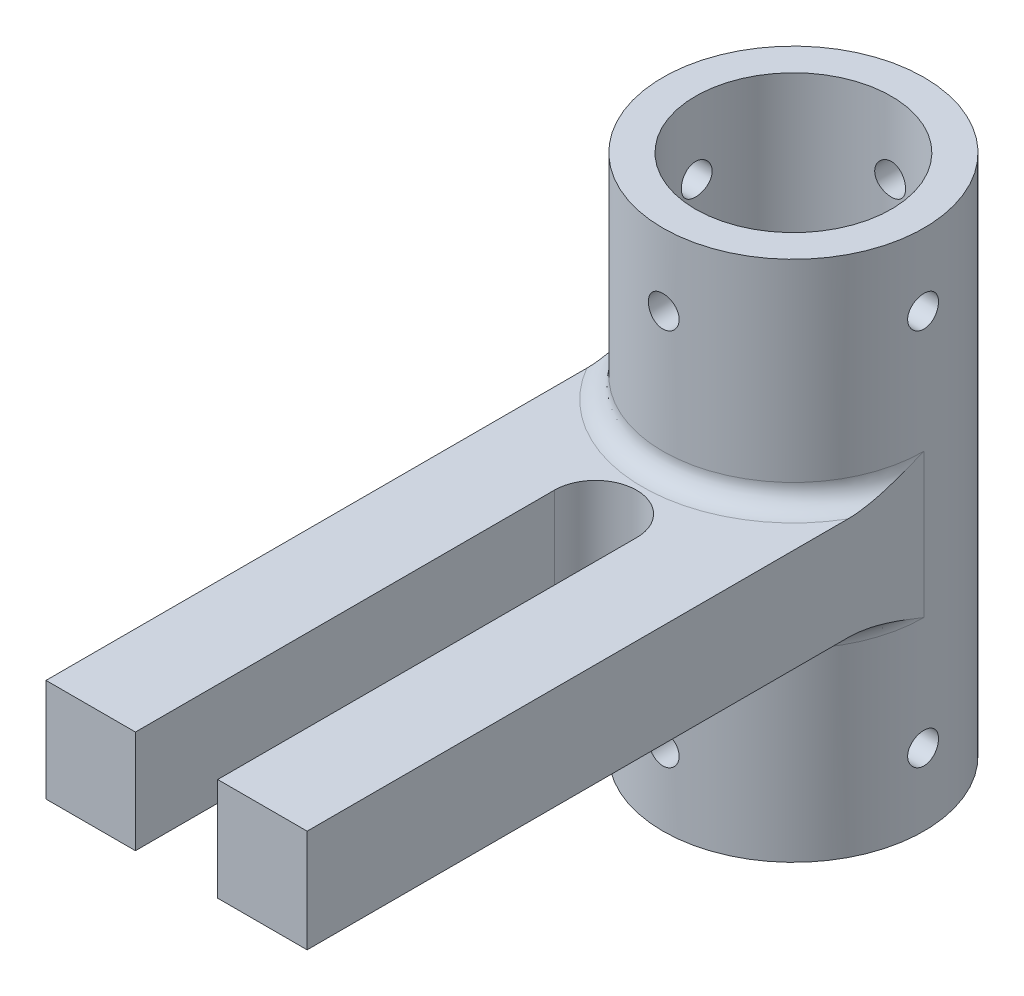
SolidWorks part; units mm, degrees
ref_plane "Front Plane" through (0, 0, 0) normal (0, 0, 1) x (1, 0, 0)
ref_plane "Top Plane" through (0, 0, 0) normal (0, 1, 0) x (1, 0, 0)
ref_plane "Right Plane" through (0, 0, 0) normal (1, 0, 0) x (0, 0, -1)
sketch "Sketch1" plane through (0, 0, 0) normal (0, 1, 0) x (1, 0, 0)
  circle A0 centre (0, 0) radius 12.7
  circle A1 centre (0, 0) radius 9.525
  dimension "D1" = 19.05
  dimension "D2" = 25.4
extrude "Boss-Extrude1" add sketch "Sketch1" along normal blind 50.8
sketch "Sketch2" plane through (0, 0, 0) normal (0, 0, 1) x (1, 0, 0)
  line L0 (-12.7, 0) -> (12.7, 0) construction
  line L1 (-12.7, 30) -> (12.7, 30)
  line L2 (-12.7, 30) -> (-12.7, 20)
  line L3 (-12.7, 20) -> (12.7, 20)
  line L4 (12.7, 30) -> (12.7, 20)
  line L5 (-12.7, 30) -> (12.7, 20) construction
  line L6 (-12.7, 20) -> (12.7, 30) construction
  point P0 (0, 25)
  point P7 (0, 0)
  dimension "D1" = 10
  dimension "D2" = 25
extrude "Boss-Extrude2" add sketch "Sketch2" against normal up to surface (60 mm away) from offset 60 up to face at (0, 50.8, 12.7)
sketch "Sketch3" plane through (0, 0, 0) normal (1, 0, 0) x (0, 0, -1)
  line L0 (12.7, 50.8) -> (-12.7, 50.8) construction
  circle A0 centre (0, 7) radius 1.5
  circle A1 centre (0, 43.8) radius 1.5
  point P7 (0, 7)
  dimension "D1" = 3
  dimension "D2" = 7
  dimension "D3" = 7
extrude "Cut-Extrude1" cut sketch "Sketch3" against normal through all both and the other way through all
pattern_circular "CirPattern1" count 2 over 90 about axis through (0, 50.8, 0) along (0, 1, 0) of "Cut-Extrude1"
sketch "Sketch4" plane through (0, 30, 0) normal (0, 1, 0) x (1, 0, 0)
  line L0 (0, -60) -> (0, -19.2549) construction
  line L1 (12.7, -60) -> (-12.7, -60) construction
  line L2 (-4, -60) -> (-4, -19.2549)
  line L3 (4, -60) -> (4, -19.2549)
  line L4 (4, -60) -> (-4, -60)
  arc A1 (4, -19.2549) -> (-4, -19.2549) centre (0, -19.2549) ccw
  point P5 (0, -60)
  dimension "D1" = 4
extrude "Cut-Extrude2" cut sketch "Sketch4" against normal through all
fillet "Fillet1" radius 2 2 edges at (0, 20, 12.7) (0, 30, 12.7)
